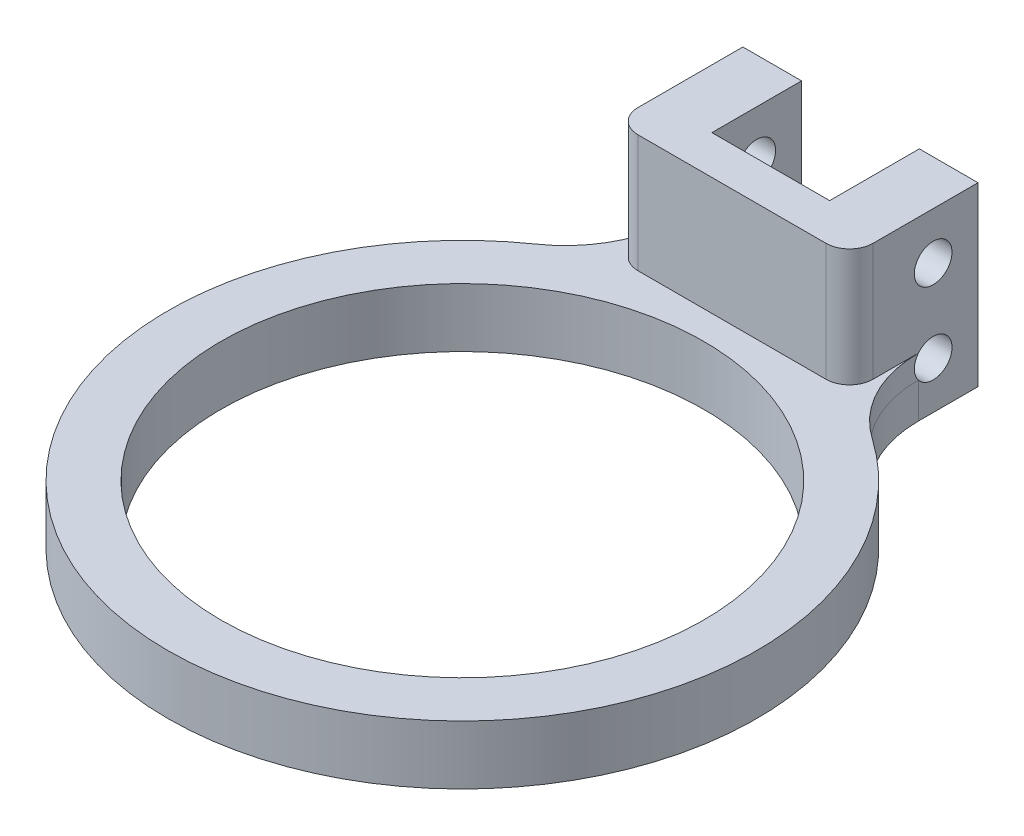
SolidWorks part; units mm, degrees
ref_plane "前视基准面" through (0, 0, 0) normal (0, 0, 1) x (1, 0, 0)
ref_plane "上视基准面" through (0, 0, 0) normal (0, 1, 0) x (1, 0, 0)
ref_plane "右视基准面" through (0, 0, 0) normal (1, 0, 0) x (0, 0, -1)
sketch "草图1" plane through (0, 0, 0) normal (0, 1, 0) x (1, 0, 0)
  circle A0 centre (0, 0) radius 20.5
  circle A2 centre (0, 0) radius 25
extrude "凸台-拉伸1" add sketch "草图1" along normal blind 5
sketch "草图2" plane through (0, 0, 0) normal (0, 1, 0) x (1, 0, 0)
  line L0 (0, 0) -> (0, 30) construction
  line L2 (-5, 33.807) -> (-9.9829, 33.807)
  line L3 (9.9829, 22.8964) -> (-9.9829, 22.8964)
  line L4 (9.9829, 22.8964) -> (9.9829, 33.807)
  line L5 (9.9829, 33.807) -> (5, 33.807)
  line L6 (-9.9829, 22.8964) -> (-9.9829, 33.807)
  line L7 (9.9829, 22.8964) -> (-9.9829, 33.807) construction
  line L8 (9.9829, 33.807) -> (-9.9829, 22.8964) construction
  line L9 (5, 26.193) -> (-5, 26.193)
  line L10 (5, 26.193) -> (5, 33.807)
  line L11 (-5, 26.193) -> (-5, 33.807)
  line L12 (5, 26.193) -> (-5, 33.807) construction
  line L13 (5, 33.807) -> (-5, 26.193) construction
  point P9 (0, 30)
  point P10 (0, 30)
extrude "凸台-拉伸2" add sketch "草图2" along normal blind 15
sketch "草图3" plane through (-9.9829, 0, 0) normal (-1, 0, 0) x (0, 0, 1)
  circle A0 centre (-30, 4) radius 1.6
  circle A1 centre (-30, 11) radius 1.6
  point P4 (0, 0)
  point P5 (0, 0)
extrude "切除-拉伸1" cut sketch "草图3" against normal through all
fillet "圆角1" radius 10 2 edges at (9.9829, 2.5, -22.9203) (-9.9829, 2.5, -22.9203)
fillet "圆角2" radius 2 2 edges at (9.9829, 10, -22.8964) (-9.9829, 10, -22.8964)
